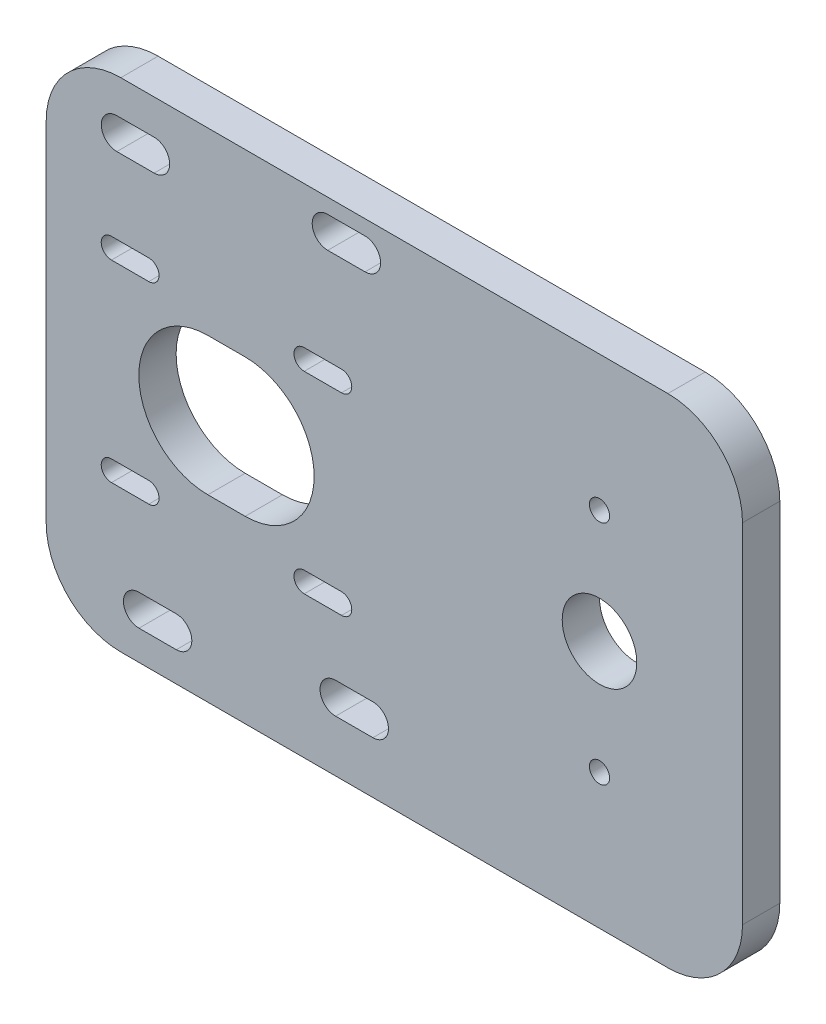
SolidWorks part; units mm, degrees
ref_plane "Alzado" through (0, 0, 0) normal (0, 0, 1) x (1, 0, 0)
ref_plane "Planta" through (0, 0, 0) normal (0, 1, 0) x (1, 0, 0)
ref_plane "Vista lateral" through (0, 0, 0) normal (1, 0, 0) x (0, 0, -1)
sketch "Croquis1" plane through (0, 0, 0) normal (0, 0, 1) x (1, 0, 0)
  line L1 (0, 0) -> (112, 0)
  line L2 (0, 0) -> (0, 80)
  line L3 (0, 80) -> (112, 80)
  line L4 (112, 0) -> (112, 80)
  dimension "D1" = 80
  dimension "D2" = 112
extrude "Saliente-Extruir1" add sketch "Croquis1" along normal blind 6
sketch "Croquis2" plane through (0, 0, 0) normal (0, 0, -1) x (-1, 0, 0)
  line L0 (0, 80) -> (0, 0) construction
  line L1 (0, 40) -> (-112, 40) construction
  line L4 (-112, 0) -> (-112, 80) construction
  line L7 (-26, 40) -> (-32, 40) construction
  line L10 (-26, 28.9) -> (-32, 28.9)
  line L19 (-26, 51.1) -> (-32, 51.1)
  line L20 (-10.5, 24.5) -> (-16.5, 24.5) construction
  line L21 (-10.5, 22.85) -> (-16.5, 22.85)
  line L22 (-10.5, 26.15) -> (-16.5, 26.15)
  line L23 (-41.5, 55.5) -> (-47.5, 55.5) construction
  line L24 (-41.5, 53.85) -> (-47.5, 53.85)
  line L25 (-41.5, 57.15) -> (-47.5, 57.15)
  line L26 (-41.5, 24.5) -> (-47.5, 24.5) construction
  line L27 (-41.5, 22.85) -> (-47.5, 22.85)
  line L28 (-41.5, 26.15) -> (-47.5, 26.15)
  line L29 (-10.5, 55.5) -> (-16.5, 55.5) construction
  line L30 (-10.5, 53.85) -> (-16.5, 53.85)
  line L31 (-10.5, 57.15) -> (-16.5, 57.15)
  line L32 (-89, 0) -> (-89, 80) construction
  line L33 (0, 0) -> (-112, 0) construction
  line L34 (-112, 80) -> (0, 80) construction
  line L35 (-58, 0) -> (-58, 80) construction
  line L36 (-46.55, 10.8347) -> (-52.55, 10.8347) construction
  line L37 (-46.55, 8.3347) -> (-52.55, 8.3347)
  line L38 (-46.55, 13.3347) -> (-52.55, 13.3347)
  line L39 (-14.924, 7.2808) -> (-20.924, 7.2808) construction
  line L40 (-14.924, 4.7808) -> (-20.924, 4.7808)
  line L41 (-14.924, 9.7808) -> (-20.924, 9.7808)
  line L42 (-45.2866, 75.0962) -> (-51.2866, 75.0962) construction
  line L43 (-45.2866, 72.5962) -> (-51.2866, 72.5962)
  line L44 (-45.2866, 77.5962) -> (-51.2866, 77.5962)
  line L45 (-11.3608, 71.8909) -> (-17.3608, 71.8909) construction
  line L46 (-11.3608, 69.3909) -> (-17.3608, 69.3909)
  line L47 (-11.3608, 74.3909) -> (-17.3608, 74.3909)
  circle A5 centre (-89, 40) radius 6
  circle A15 centre (-89, 21.75) radius 1.625
  circle A16 centre (-89, 58.25) radius 1.625
  arc A19 (-26, 28.9) -> (-26, 51.1) centre (-26, 40) ccw
  arc A20 (-32, 51.1) -> (-32, 28.9) centre (-32, 40) ccw
  arc A21 (-10.5, 22.85) -> (-10.5, 26.15) centre (-10.5, 24.5) ccw
  arc A22 (-16.5, 26.15) -> (-16.5, 22.85) centre (-16.5, 24.5) ccw
  arc A23 (-41.5, 53.85) -> (-41.5, 57.15) centre (-41.5, 55.5) ccw
  arc A24 (-47.5, 57.15) -> (-47.5, 53.85) centre (-47.5, 55.5) ccw
  arc A25 (-41.5, 22.85) -> (-41.5, 26.15) centre (-41.5, 24.5) ccw
  arc A26 (-47.5, 26.15) -> (-47.5, 22.85) centre (-47.5, 24.5) ccw
  arc A27 (-10.5, 53.85) -> (-10.5, 57.15) centre (-10.5, 55.5) ccw
  arc A28 (-16.5, 57.15) -> (-16.5, 53.85) centre (-16.5, 55.5) ccw
  arc A29 (-46.55, 8.3347) -> (-46.55, 13.3347) centre (-46.55, 10.8347) ccw
  arc A30 (-52.55, 13.3347) -> (-52.55, 8.3347) centre (-52.55, 10.8347) ccw
  arc A31 (-14.924, 4.7808) -> (-14.924, 9.7808) centre (-14.924, 7.2808) ccw
  arc A32 (-20.924, 9.7808) -> (-20.924, 4.7808) centre (-20.924, 7.2808) ccw
  arc A33 (-45.2866, 72.5962) -> (-45.2866, 77.5962) centre (-45.2866, 75.0962) ccw
  arc A34 (-51.2866, 77.5962) -> (-51.2866, 72.5962) centre (-51.2866, 75.0962) ccw
  arc A35 (-11.3608, 69.3909) -> (-11.3608, 74.3909) centre (-11.3608, 71.8909) ccw
  arc A36 (-17.3608, 74.3909) -> (-17.3608, 69.3909) centre (-17.3608, 71.8909) ccw
  point P6 (-29, 40)
  point P19 (-13.5, 24.5)
  point P28 (-44.5, 55.5)
  point P35 (-44.5, 24.5)
  point P41 (-49.55, 10.8347)
  point P48 (-13.5, 55.5)
  point P63 (-17.924, 7.2808)
  point P72 (-48.2866, 75.0962)
  point P79 (-14.3608, 71.8909)
  point P84 (-6.8811, 76.4488)
  point P85 (-6.8811, 76.4488)
  point P86 (-6.8811, 76.4488)
  point P87 (-17.924, 7.2808)
  point P88 (-14.3608, 71.8909)
  dimension "D2" = 6
  dimension "D3" = 11.1
  dimension "D4" = 3.3
  dimension "D5" = 6
  dimension "D6" = 12
  dimension "D13" = 3.25
  dimension "D14" = 3.25
  dimension "D29" = 2.5
  dimension "D32" = 2.5
  dimension "D34" = 2.5
  dimension "D36" = 2.5
  dimension "D7" = 15.5
  dimension "D8" = 15.5
  dimension "D9" = 3.3
  dimension "D10" = 6
  dimension "D11" = 23
  dimension "D12" = 40
  dimension "D15" = 18.25
  dimension "D16" = 18.25
  dimension "D17" = 3.3
  dimension "D18" = 6
  dimension "D19" = 3.3
  dimension "D20" = 6
  dimension "D21" = 15.5
  dimension "D22" = 15.5
  dimension "D23" = 15.5
  dimension "D24" = 15.5
  dimension "D25" = 15.5
  dimension "D26" = 15.5
  dimension "D27" = 60
  dimension "D28" = 26
  dimension "D30" = 6
  dimension "D31" = 6
  dimension "D33" = 6
  dimension "D35" = 6
extrude "Cortar-Extruir1" cut sketch "Croquis2" against normal through all
fillet "Redondeo1" radius 12 4 edges at (112, 0, 3) (112, 80, 3) (0, 0, 3) (0, 80, 3)
